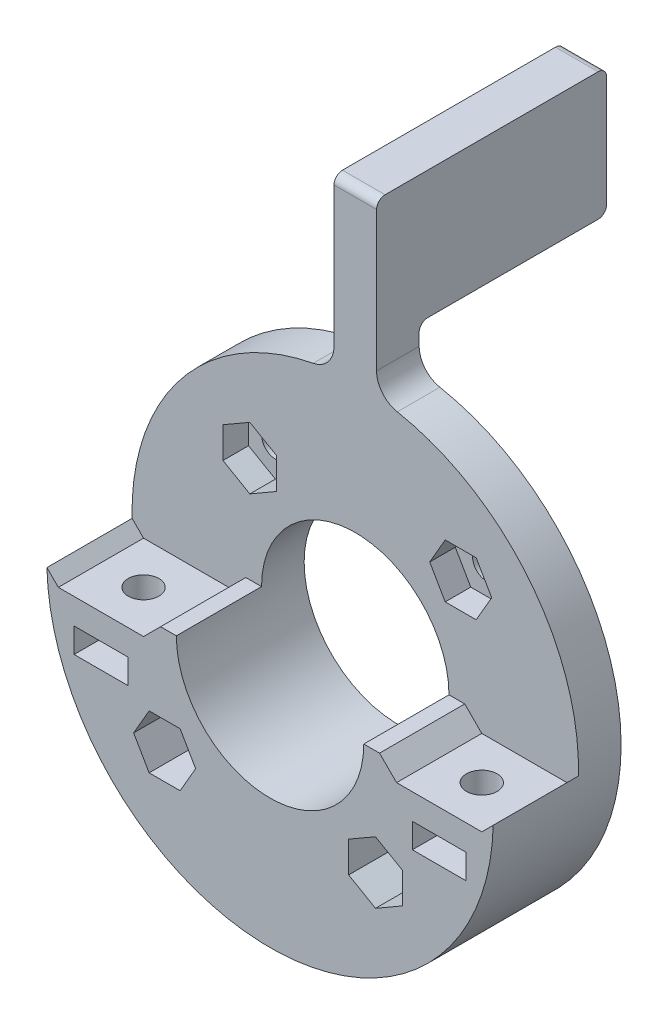
SolidWorks part; units mm, degrees
ref_plane "Plano frontal" through (0, 0, 0) normal (0, 0, 1) x (1, 0, 0)
ref_plane "Plano superior" through (0, 0, 0) normal (0, 1, 0) x (1, 0, 0)
ref_plane "Plano direito" through (0, 0, 0) normal (1, 0, 0) x (0, 0, -1)
sketch "Esboço1" plane through (0, 0, 0) normal (0, 0, 1) x (1, 0, 0)
  circle A2 centre (0, 0) radius 28.7
  dimension "D3" = 57.4
extrude "Ressalto-extrusão1" add sketch "Esboço1" along normal mid plane 10
sketch "Esboço2" plane through (0, 0, 5) normal (0, 0, 1) x (1, 0, 0)
  circle A0 centre (0, 0) radius 11
  dimension "D1" = 22
extrude "Corte-extrusão1" cut sketch "Esboço2" against normal blind 8
sketch "Esboço3" plane through (0, 0, -5) normal (0, 0, -1) x (-1, 0, 0)
  circle A0 centre (0, 0) radius 7.5
  dimension "D1" = 15
extrude "Corte-extrusão2" cut sketch "Esboço3" against normal through all
sketch "Esboço8" plane through (0, 0, 5) normal (0, 0, 1) x (1, 0, 0)
  line L0 (-11, 0) -> (-28.7, 0)
  line L1 (11, 0) -> (28.7, 0)
  arc A0 (-11, 0) -> (11, 0) centre (0, 0) ccw
  circle A1 centre (0, 0) radius 11 construction
  arc A2 (-28.7, 0) -> (28.7, 0) centre (0, 0) ccw
  circle A3 centre (0, 0) radius 28.7 construction
extrude "Ressalto-extrusão4" add sketch "Esboço8" along normal blind 10
sketch "Esboço9" plane through (0, 0, 15) normal (0, 0, 1) x (1, 0, 0)
  line L0 (-11, 0) -> (-28.7, 0) construction
  line L1 (0, -5.5) -> (0, 5.5) construction
  line L2 (-11, 0) -> (-28.7, 0) construction
  line L3 (-14.85, 0) -> (-24.85, 0)
  line L4 (-14.85, 0) -> (-14.85, -2)
  line L5 (-14.85, -2) -> (-24.85, -2)
  line L6 (-24.85, 0) -> (-24.85, -2)
  line L7 (24.85, 0) -> (24.85, -2)
  line L8 (14.85, -2) -> (24.85, -2)
  line L9 (14.85, 0) -> (14.85, -2)
  line L10 (14.85, 0) -> (24.85, 0)
  point P7 (-19.85, 0)
  point P10 (-19.85, 0)
  dimension "D1" = 10
  dimension "D2" = 2
extrude "Corte-extrusão5" cut sketch "Esboço9" against normal up to surface (10 mm away) up to face at (0, 9.925, 5)
chamfer "Chanfro1" distance 2 angle 45 4 edges at (24.85, 0, 10) (14.85, 0, 10) (-14.85, 0, 10) (-24.85, 0, 10)
sketch "Esboço10" plane through (0, -2, 0) normal (0, 1, 0) x (1, 0, 0)
  line L0 (-24.85, -15) -> (-14.85, -15) construction
  line L1 (-14.85, -5) -> (-14.85, -15) construction
  line L2 (0, -5.5) -> (0, 5.5) construction
  circle A0 centre (-19.85, -10) radius 1.8
  circle A2 centre (19.85, -10) radius 1.8
  point P4 (-19.85, -15)
  point P7 (-14.85, -10)
  dimension "D1" = 3.6
extrude "Corte-extrusão6" cut sketch "Esboço10" against normal blind 10
sketch "Esboço11" plane through (0, -2, 0) normal (0, 1, 0) x (1, 0, 0)
  line L0 (-23, -8.1813) -> (-23, -11.8187)
  line L1 (-23, -11.8187) -> (-19.85, -13.6373) construction
  line L2 (-19.85, -13.6373) -> (-16.7, -11.8187) construction
  line L3 (-16.7, -11.8187) -> (-16.7, -8.1813)
  line L4 (-16.7, -8.1813) -> (-19.85, -6.3627)
  line L5 (-19.85, -6.3627) -> (-23, -8.1813)
  line L6 (-16.7, -11.8187) -> (-16.7, -15)
  line L7 (-24.85, -15) -> (-14.85, -15) construction
  line L8 (-16.7, -15) -> (-23, -15)
  line L9 (-23, -15) -> (-23, -11.8187)
  line L10 (0, -5.5) -> (0, 5.5) construction
  line L11 (19.85, -13.6373) -> (16.7, -11.8187) construction
  line L12 (23, -11.8187) -> (19.85, -13.6373) construction
  line L13 (23, -15) -> (23, -11.8187)
  line L14 (16.7, -15) -> (23, -15)
  line L15 (16.7, -11.8187) -> (16.7, -15)
  line L16 (19.85, -6.3627) -> (23, -8.1813)
  line L17 (16.7, -8.1813) -> (19.85, -6.3627)
  line L18 (16.7, -11.8187) -> (16.7, -8.1813)
  line L19 (23, -8.1813) -> (23, -11.8187)
  circle A0 centre (-19.85, -10) radius 3.6373 construction
  circle A1 centre (19.85, -10) radius 3.6373 construction
  dimension "D1" = 6.3
extrude "Corte-extrusão7" cut sketch "Esboço11" against normal blind 2.9 from offset 3 offset against normal yes
sketch "Esboço13" plane through (0, 0, -5) normal (0, 0, -1) x (-1, 0, 0)
  circle A0 centre (0, 0) radius 28.7
  circle A1 centre (0, 0) radius 28.7 construction
extrude "Corte-extrusão8" cut sketch "Esboço13" against normal blind 5
sketch "Esboço14" plane through (0, 0, 0) normal (0, 0, -1) x (-1, 0, 0)
  circle A0 centre (0, 0) radius 28.7
  circle A1 centre (0, 0) radius 28.7 construction
  circle A2 centre (0, 0) radius 26.2
  dimension "D1" = 2.5
extrude "Corte-extrusão9" cut sketch "Esboço14" against normal through all
sketch "Esboço15" plane through (0, 0, 0) normal (0, 0, -1) x (-1, 0, 0)
  line L0 (0, 0) -> (0, 26.2) construction
  line L1 (0, 0) -> (-18.5262, 18.5262) construction
  circle A0 centre (0, 0) radius 26.2 construction
  circle A1 centre (-12.3744, 12.3744) radius 1.6
  circle A2 centre (12.3744, 12.3744) radius 1.6
  circle A3 centre (12.3744, -12.3744) radius 1.6
  circle A4 centre (-12.3744, -12.3744) radius 1.6
  point P18 (0, 0)
  dimension "D1" = 3.2
  dimension "D2" = 45
  dimension "D3" = 17.5
  dimension "D4" = 4
extrude "Corte-extrusão10" cut sketch "Esboço15" against normal through all
sketch "Esboço17" plane through (0, 0, 5) normal (0, 0, 1) x (1, 0, 0)
  line L0 (-15.5244, 14.193) -> (-15.5244, 10.5557)
  line L1 (-15.5244, 10.5557) -> (-12.3744, 8.7371)
  line L2 (-12.3744, 8.7371) -> (-9.2244, 10.5557)
  line L3 (-9.2244, 10.5557) -> (-9.2244, 14.193)
  line L4 (-9.2244, 14.193) -> (-12.3744, 16.0117)
  line L5 (-12.3744, 16.0117) -> (-15.5244, 14.193)
  line L6 (16.0117, 12.3744) -> (14.193, 15.5244)
  line L7 (14.193, 15.5244) -> (10.5557, 15.5244)
  line L8 (10.5557, 15.5244) -> (8.7371, 12.3744)
  line L9 (8.7371, 12.3744) -> (10.5557, 9.2244)
  line L10 (10.5557, 9.2244) -> (14.193, 9.2244)
  line L11 (14.193, 9.2244) -> (16.0117, 12.3744)
  line L12 (12.3744, -16.0117) -> (15.5244, -14.193)
  line L13 (15.5244, -14.193) -> (15.5244, -10.5557)
  line L14 (15.5244, -10.5557) -> (12.3744, -8.7371)
  line L15 (12.3744, -8.7371) -> (9.2244, -10.5557)
  line L16 (9.2244, -10.5557) -> (9.2244, -14.193)
  line L17 (9.2244, -14.193) -> (12.3744, -16.0117)
  line L18 (-16.0117, -12.3744) -> (-14.193, -15.5244)
  line L19 (-14.193, -15.5244) -> (-10.5557, -15.5244)
  line L20 (-10.5557, -15.5244) -> (-8.7371, -12.3744)
  line L21 (-8.7371, -12.3744) -> (-10.5557, -9.2244)
  line L22 (-10.5557, -9.2244) -> (-14.193, -9.2244)
  line L23 (-14.193, -9.2244) -> (-16.0117, -12.3744)
  circle A0 centre (-12.3744, 12.3744) radius 3.6373 construction
  arc A1 (26.1917, -0.6583) -> (-26.1917, -0.6583) centre (0, 0) ccw construction
  point P30 (0, 0)
  dimension "D1" = 6.3
  dimension "D2" = 4
extrude "Corte-extrusão11" cut sketch "Esboço17" along normal through all from offset 3 offset against normal yes
sketch "Esboço18" plane through (0, 0, 5) normal (0, 0, 1) x (1, 0, 0)
  line L0 (-2.5, 26.0805) -> (-2.5, 46.0805)
  line L5 (-2.5, 46.0805) -> (2.5, 46.0805)
  line L6 (2.5, 46.0805) -> (2.5, 26.0805)
  arc A0 (26.1917, -0.6583) -> (-26.1917, -0.6583) centre (0, 0) ccw construction
  arc A1 (2.5, 26.0805) -> (-2.5, 26.0805) centre (0, 0) ccw
  point P5 (0, 46.0805)
  dimension "D1" = 5
  dimension "D2" = 20
extrude "Ressalto-extrusão5" add sketch "Esboço18" against normal blind 5
sketch "Esboço19" plane through (2.5, 0, 0) normal (1, 0, 0) x (0, 0, -1)
  line L0 (0, 26.0805) -> (-5, 26.0805) construction
  line L1 (0, 46.0805) -> (22, 46.0805)
  line L2 (0, 46.0805) -> (0, 31.0805)
  line L3 (0, 31.0805) -> (22, 31.0805)
  line L4 (22, 46.0805) -> (22, 31.0805)
  dimension "D1" = 22
  dimension "D2" = 5
extrude "Ressalto-extrusão6" add sketch "Esboço19" against normal blind 5
fillet "Filete1" radius 3 2 edges at (-2.5, 26.0805, 2.5) (2.5, 26.0805, 2.5)
fillet "Filete2" radius 1 1 edges at (0, 31.0805, 0)
fillet "Filete3" radius 1 3 edges at (0, 46.0805, 5) (0, 31.0805, -22) (0, 46.0805, -22)
